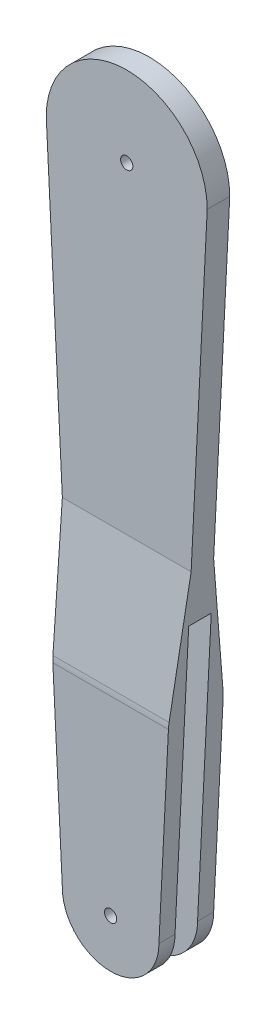
SolidWorks part; units mm, degrees
ref_plane "Front Plane" through (0, 0, 0) normal (0, 0, 1) x (1, 0, 0)
ref_plane "Top Plane" through (0, 0, 0) normal (0, 1, 0) x (1, 0, 0)
ref_plane "Right Plane" through (0, 0, 0) normal (1, 0, 0) x (0, 0, -1)
sketch "Sketch2" plane through (0, 0, 0) normal (0, 0, 1) x (1, 0, 0)
  line L1 (15, -200) -> (25, 0)
  line L2 (-15, -200) -> (-25, 0)
  line L3 (0, -200) -> (0, -397.2479)
  line L4 (0, -170) -> (0, -200)
  arc A2 (25, 0) -> (-25, 0) centre (0, 0) ccw
  arc A4 (-15, -200) -> (15, -200) centre (0, -200) ccw
  dimension "D1" = 200
  dimension "D2" = 50
  dimension "D3" = 15
extrude "Boss-Extrude1" add sketch "Sketch2" along normal blind 7 contours L2 A4 L1 A2 region at (0, -85.2531, 0)
ref_plane "Plane1" through (0, 0, 3.5) normal (0, 0, 1) x (1, 0, 0)
sketch "Sketch6" plane through (0, 0, 7) normal (0, 0, 1) x (1, 0, 0)
  circle A0 centre (0, -200) radius 2.25
  dimension "D1" = 4.5
extrude "Cut-Extrude4" cut sketch "Sketch6" against normal blind 25
ref_plane "Plane2" through (0, 0, 0) normal (-1, 0, 0) x (0, 0, 1)
sketch "Sketch9" plane through (0, 0, 0) normal (-1, 0, 0) x (0, 0, 1)
  line L0 (0, -200) -> (0, -215)
  line L1 (0, -200) -> (0, -215) construction
  line L2 (0, -215) -> (-5, -215)
  line L3 (-5, -215) -> (-5, -140)
  line L4 (-5, -140) -> (0, -100)
  line L5 (0, -200) -> (0, 0) construction
  line L6 (0, -200) -> (0, -100)
  dimension "D1" = 15
  dimension "D2" = 5
  dimension "D3" = 75
extrude "Boss-Extrude2" add sketch "Sketch9" along normal blind 22 and the other way blind 21
sketch "Sketch10" plane through (0, 0, 7) normal (0, 0, 1) x (1, 0, 0)
  line L0 (20, -100) -> (21, -100)
  line L1 (15, -200) -> (25, 0) construction
  line L2 (21, -100) -> (21, -215)
  line L3 (21, -215) -> (-22, -215)
  line L4 (-22, -215) -> (-22, -100)
  line L5 (-22, -100) -> (-20, -100)
  line L6 (-15, -200) -> (-25, 0) construction
  line L7 (-20, -100) -> (-15, -200)
  line L8 (15, -200) -> (20, -100)
  arc A0 (-15, -200) -> (15, -200) centre (0, -200) ccw
  arc M10 (-15, -200) -> (15, -200) centre (0, -200) ccw
  line M11 (15, -200) -> (25, 0)
  line M13 (-25, 0) -> (-15, -200)
extrude "Cut-Extrude5" cut sketch "Sketch10" against normal mid plane 56 contours L3 L2 L0 M11 M10 | L5 L4 L3 M10 M13 region at (-18.7114, -171.8486, 7) region at (18.0547, -175.2279, 7)
fillet "Fillet1" radius 15 1 edges at (0, -140, -5)
mirror "Mirror1" about plane through (0, 0, 3.5) normal (0, 0, 1) of "Fillet1", "Boss-Extrude2"
mirror "Mirror2" about plane through (0, 0, 3.5) normal (0, 0, 1) of "Cut-Extrude5"
sketch "Sketch12" plane through (0, 0, 0) normal (-1, 0, 0) x (0, 0, 1)
  line L0 (-5, -215) -> (12, -215) construction
  line L1 (0, -215) -> (7, -215)
  line L2 (0, -215) -> (0, -115)
  line L3 (0, -115) -> (7, -115)
  line L4 (7, -215) -> (7, -115)
  line L5 (12, -215) -> (12, -200) construction
  dimension "D1" = 7
  dimension "D2" = 5
  dimension "D3" = 100
extrude "Cut-Extrude6" cut sketch "Sketch12" along normal mid plane 49
sketch "Sketch13" plane through (0, 0, -5) normal (0, 0, -1) x (-1, 0, 0)
  circle A0 centre (0, -200) radius 1.9
  dimension "D1" = 3.8
extrude "Cut-Extrude7" cut sketch "Sketch13" against normal mid plane 49
sketch "Sketch14" plane through (0, 0, 0) normal (0, 0, -1) x (-1, 0, 0)
  circle A0 centre (0, 0) radius 1.9
  dimension "D1" = 3.8
extrude "Cut-Extrude8" cut sketch "Sketch14" against normal blind 7
